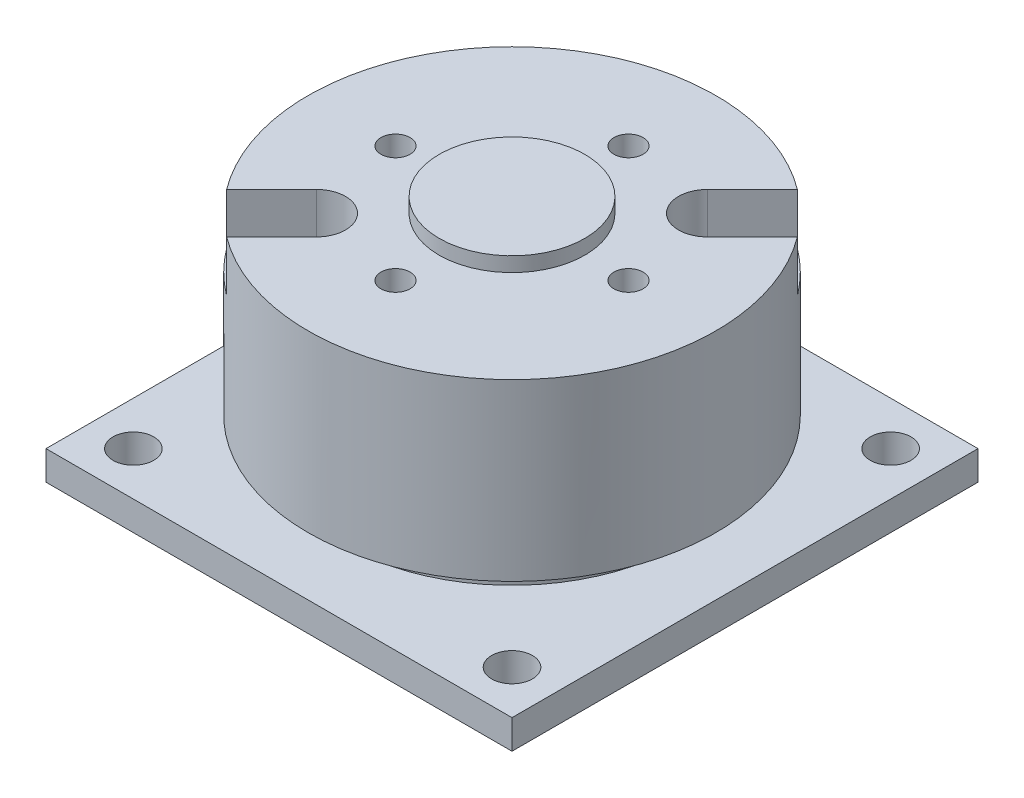
SolidWorks part; units mm, degrees
ref_plane "前视基准面" through (0, 0, 0) normal (0, 0, 1) x (1, 0, 0)
ref_plane "上视基准面" through (0, 0, 0) normal (0, 1, 0) x (1, 0, 0)
ref_plane "右视基准面" through (0, 0, 0) normal (1, 0, 0) x (0, 0, -1)
other "Configuration Table"
sketch "草图1" plane through (0, 0, 0) normal (0, 1, 0) x (1, 0, 0)
  line L0 (0, 0) -> (5, 0) construction
  circle A0 centre (0, 0) radius 11.5
  circle A1 centre (0, 0) radius 8 construction
  circle A2 centre (0, 0) radius 5
  circle A3 centre (8, 0) radius 1
  circle A4 centre (0, -8) radius 1
  circle A5 centre (-8, 0) radius 1
  circle A6 centre (0, 8) radius 1
  dimension "D1" = 23
  dimension "D2" = 16
  dimension "D3" = 10
  dimension "D4" = 2
  dimension "D5" = 4
extrude "凸台-拉伸1" add sketch "草图1" along normal blind 2 contours A2 | A0 A6 A5 A4 A3 A2 region at (-11.1747, 0, 0) region at (0, 0, 0)
extrude "凸台-拉伸2" add sketch "草图1<3>" against normal blind 0.25 contours A2 region at (0, 0, 0)
sketch "草图1<3>" plane through (0, 0, 0) normal (0, 1, 0) x (1, 0, 0) same geometry as "草图1"
sketch "草图2" plane through (0, 2, 0) normal (0, 1, 0) x (1, 0, 0)
  circle A0 centre (0, 0) radius 14
  dimension "D1" = 28
extrude "凸台-拉伸3" add sketch "草图2" along normal blind 12
sketch "草图3" plane through (0, 14, 0) normal (0, 1, 0) x (1, 0, 0)
  circle A0 centre (0, 0) radius 8 construction
  circle A1 centre (0, 0) radius 5
  circle A2 centre (8, 0) radius 1
  circle A3 centre (0, -8) radius 1
  circle A4 centre (-8, 0) radius 1
  circle A5 centre (0, 8) radius 1
  dimension "D1" = 16
  dimension "D2" = 10
  dimension "D3" = 2
  dimension "D4" = 4
extrude "凸台-拉伸4" add sketch "草图3" along normal blind 1 contours A1 region at (0, 14, 0)
extrude "切除-拉伸1" cut sketch "草图3<3>" against normal blind 10 contours A2 | A5 | A4 | A3 region at (8, 14, 0) region at (-8, 14, 0) region at (0, 14, -8)
sketch "草图3<3>" plane through (0, 14, 0) normal (0, 1, 0) x (1, 0, 0) same geometry as "草图3"
sketch "草图4" plane through (0, 14, 0) normal (0, 1, 0) x (1, 0, 0)
  line L0 (0, 0) -> (9.8995, 9.8995) construction
  line L1 (0, 0) -> (5, 0) construction
  line L2 (13.0815, 13.0815) -> (6.7175, 6.7175) construction
  line L3 (14.4957, 11.6673) -> (8.1317, 5.3033)
  line L4 (11.6673, 14.4957) -> (5.3033, 8.1317)
  line L5 (0, 0) -> (3.5355, -3.5355) construction
  line L6 (-13.0815, -13.0815) -> (-6.7175, -6.7175) construction
  line L7 (-11.6673, -14.4957) -> (-5.3033, -8.1317)
  line L8 (-14.4957, -11.6673) -> (-8.1317, -5.3033)
  circle A0 centre (0, 0) radius 14 construction
  circle A1 centre (0, 0) radius 5 construction
  arc A2 (14.4957, 11.6673) -> (11.6673, 14.4957) centre (13.0815, 13.0815) ccw
  arc A3 (5.3033, 8.1317) -> (8.1317, 5.3033) centre (6.7175, 6.7175) ccw
  arc A4 (-11.6673, -14.4957) -> (-14.4957, -11.6673) centre (-13.0815, -13.0815) cw
  arc A5 (-8.1317, -5.3033) -> (-5.3033, -8.1317) centre (-6.7175, -6.7175) cw
  point P10 (9.8995, 9.8995)
  point P18 (-9.8995, -9.8995)
  point P23 (-5.3033, -5.3033)
  dimension "D1" = 45
  dimension "D2" = 4
  dimension "D3" = 17
extrude "切除-拉伸2" cut sketch "草图4" against normal blind 3.5
sketch "草图5" plane through (0, 0, 0) normal (0, -1, 0) x (1, 0, 0)
  line L0 (0, 0) -> (16, 0) construction
  line L1 (-16, 16) -> (16, 16)
  line L2 (-16, 16) -> (-16, -16)
  line L3 (-16, -16) -> (16, -16)
  line L4 (16, 16) -> (16, -16)
  line L5 (0, 0) -> (0, 16) construction
  circle A0 centre (0, 0) radius 16 construction
  circle A1 centre (13, 13) radius 1.4
  circle A2 centre (-13, 13) radius 1.4
  circle A3 centre (13, -13) radius 1.4
  circle A4 centre (-13, -13) radius 1.4
  dimension "D1" = 32
  dimension "D2" = 2.8
  dimension "D3" = 26
  dimension "D4" = 26
extrude "凸台-拉伸5" add sketch "草图5" along normal blind 2
sketch "草图6" plane through (0, -2, 0) normal (0, -1, 0) x (1, 0, 0)
  circle A0 centre (0, 0) radius 8 construction
  circle A1 centre (8, 0) radius 1
  circle A2 centre (0, -8) radius 1
  circle A3 centre (-8, 0) radius 1
  circle A4 centre (0, 8) radius 1
  dimension "D1" = 16
  dimension "D2" = 2
  dimension "D3" = 4
extrude "凸台-拉伸6" add sketch "草图6" along normal blind 2
sketch "草图7" plane through (0, -4, 0) normal (0, -1, 0) x (1, 0, 0)
  line L0 (0, 0) -> (10, 0) construction
  line L1 (-10, 10) -> (10, 10)
  line L2 (-10, 10) -> (-10, -10)
  line L3 (-10, -10) -> (10, -10)
  line L4 (10, 10) -> (10, -10)
  line L5 (0, 0) -> (0, 10) construction
  circle A0 centre (7, 7) radius 1.6
  circle A1 centre (-7, 7) radius 1.6
  circle A2 centre (7, -7) radius 1.6
  circle A3 centre (-7, -7) radius 1.6
  dimension "D5" = 3.2
  dimension "D1" = 20
  dimension "D2" = 20
  dimension "D3" = 10
  dimension "D4" = 10
  dimension "D6" = 14
  dimension "D7" = 14
extrude "凸台-拉伸7" add sketch "草图7" along normal blind 1.7
